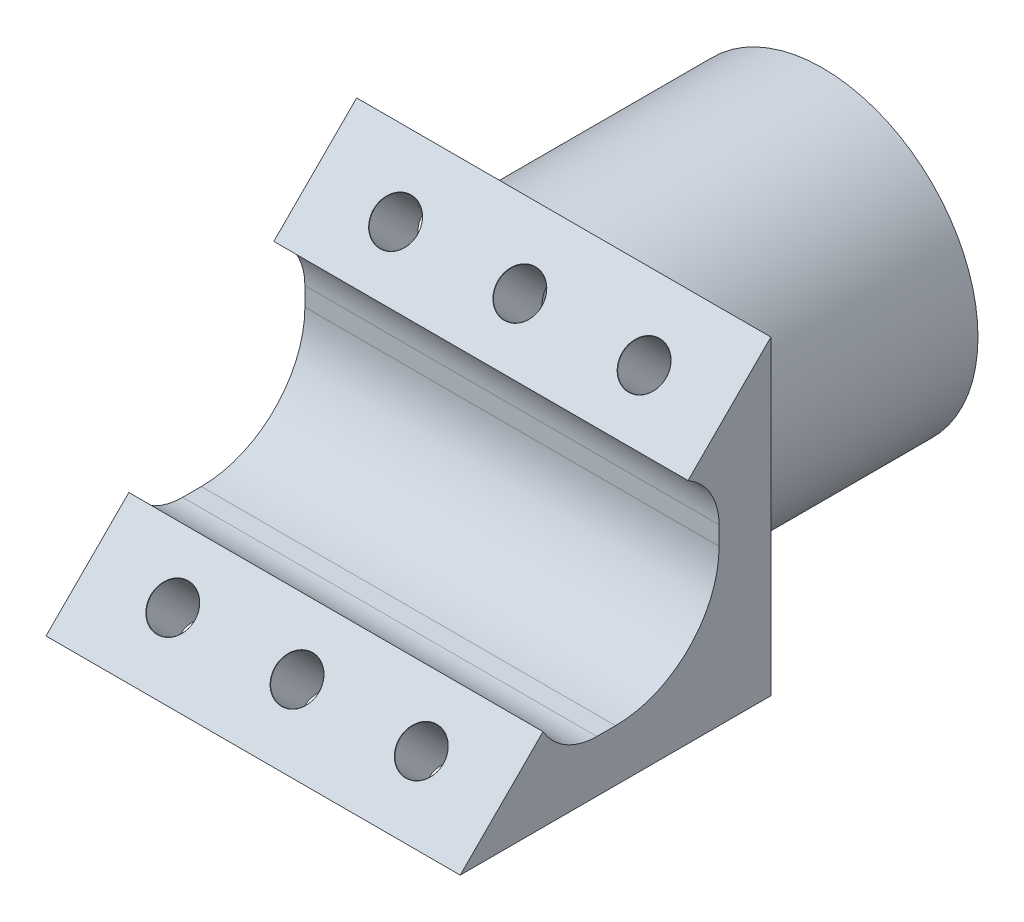
SolidWorks part; units mm, degrees
ref_plane "Front Plane" through (0, 0, 0) normal (0, 0, 1) x (1, 0, 0)
ref_plane "Top Plane" through (0, 0, 0) normal (0, 1, 0) x (1, 0, 0)
ref_plane "Right Plane" through (0, 0, 0) normal (1, 0, 0) x (0, 0, -1)
sketch "Sketch1" plane through (0, 0, 0) normal (0, 0, 1) x (1, 0, 0)
  circle A0 centre (0, 0) radius 10
  circle A1 centre (0, 0) radius 15
  dimension "D1" = 20
  dimension "D2" = 5
extrude "Boss-Extrude1" add sketch "Sketch1" along normal blind 25 contours A1 A0 region at (-14.5757, 0, 0)
sketch "Sketch2" plane through (0, 0, 25) normal (0, 0, 1) x (1, 0, 0)
  line L0 (0, 15) -> (0, 0) construction
  line L1 (-20, 15) -> (20, 15)
  line L2 (-20, 15) -> (-20, -15)
  line L3 (-20, -15) -> (20, -15)
  line L4 (20, 15) -> (20, -15)
  circle A0 centre (0, 0) radius 15 construction
  dimension "D1" = 40
extrude "Boss-Extrude2" add sketch "Sketch2" along normal blind 30
sketch "Sketch3" plane through (-20, 0, 0) normal (-1, 0, 0) x (0, 0, 1)
  line L0 (25, 15) -> (55, -15) construction
  line L1 (55, -15) -> (55, 15) construction
  line L2 (55, 15) -> (25, -15) construction
  circle A0 centre (40, 0) radius 10
  dimension "D1" = 20
extrude "Cut-Extrude1" cut sketch "Sketch3" against normal through all
sketch "Sketch4" plane through (20, 0, 0) normal (1, 0, 0) x (0, 0, -1)
  line L0 (-30, 0) -> (-30, 15)
  line L1 (-55, 15) -> (-25, 15) construction
  line L2 (-40, -10) -> (-55, -10)
  line L3 (-55, -15) -> (-55, 15) construction
  line L4 (-55, -10) -> (-55, 15)
  line L5 (-55, 15) -> (-30, 15)
  circle A0 centre (-40, 0) radius 10 construction
  arc A1 (-30, 0) -> (-40, -10) centre (-40, 0) cw
extrude "Cut-Extrude2" cut sketch "Sketch4" against normal through all
sketch "Sketch5" plane through (0, 15, 0) normal (0, 1, 0) x (1, 0, 0)
  line L0 (-21, -24) -> (-21, -31)
  line L1 (-21, -31) -> (21, -31)
  line L2 (21, -31) -> (21, -24)
  line L3 (21, -24) -> (0, -24)
  line L4 (0, -24) -> (-21, -24)
  line L5 (-20, -25) -> (-20, -30)
  line L6 (-20, -30) -> (20, -30)
  line L7 (20, -30) -> (20, -25)
  line L8 (20, -25) -> (0, -25)
  line L9 (0, -25) -> (-20, -25)
  line L10 (-20, -25) -> (-20, -30) construction
  line L11 (-20, -30) -> (20, -30) construction
  line L12 (20, -30) -> (20, -25) construction
  line L13 (20, -25) -> (0, -25) construction
  line L14 (0, -25) -> (-20, -25) construction
  dimension "D1" = 0
  dimension "D2" = 1
extrude "Cut-Extrude5" [suppressed] cut sketch "Sketch5" against normal blind 6
sketch "Sketch6" plane through (20, 0, 0) normal (1, 0, 0) x (0, 0, -1)
  line L0 (-25, 15) -> (-30, 10)
  line L1 (-30, 0) -> (-30, 15) construction
  line L2 (-30, 10) -> (-30, 15)
  line L3 (-30, 15) -> (-25, 15)
  line L4 (-55, -10) -> (-55, -15)
  line L5 (-55, -10) -> (-50, -10)
  line L7 (-55, -10) -> (-40, -10) construction
  line L8 (-50, -10) -> (-55, -15)
extrude "Cut-Extrude6" cut sketch "Sketch6" against normal through all
sketch "Sketch7" plane through (-20, 0, 0) normal (-1, 0, 0) x (0, 0, 1)
  line L0 (30, 10) -> (33, 7)
  line L1 (33, 7) -> (30, 7)
  line L2 (30, 0) -> (30, 10) construction
  line L3 (30, 7) -> (30, 10)
  line L4 (50, -10) -> (47, -7)
  line L5 (47, -7) -> (47, -10)
  line L6 (50, -10) -> (40, -10) construction
  line L7 (47, -10) -> (50, -10)
  dimension "D1" = 3
extrude "Boss-Extrude3" add sketch "Sketch7" against normal up to surface (40 mm away) up to face at (20, -3.8673, 36.1327)
fillet "Fillet1" radius 6 2 edges at (0, -10, 47) (0, 7, 30)
sketch "Sketch8" plane through (0, 20, 20) normal (0, 0.7071, 0.7071) x (1, 0, 0)
  point P0 (12, -43.4975)
  point P3 (0, -43.4975)
  point P6 (-12, -43.4975)
  point P9 (-12, -13.0711)
  point P12 (0, -13.0711)
  point P15 (12, -13.0711)
hole_wizard "Ø4.2 (4.2) Diameter Hole1" positions "Sketch8" profile "Sketch10" hole size "Ø4.2" standard "DIN"
sketch "Sketch10" plane through (12, -10.7574, 50.7574) normal (1, 0, 0) x (0, -0.7071, 0.7071)
  line L0 (0, 0) -> (0, 7.2618)
  line L1 (0, 7.2618) -> (2.1, 6)
  line L2 (2.1, 6) -> (2.1, 0.025)
  line L3 (2.1, 0.025) -> (2.125, 0)
  line L5 (2.125, 0) -> (0, 0)
  line L6 (-2.1, 0.025) -> (-2.125, 0) construction
  line L10 (0, 7.2618) -> (-2.1, 6) construction
  line L11 (0, -6.35) -> (0, 107.95) construction
  dimension "Hole Dia." = 4.2
  dimension "Hole Depth" = 6
  dimension "Near C'Sink Dia." = 4.25
  dimension "Near C'Sink Angle" = 90
  dimension "Drill Angle" = 118
